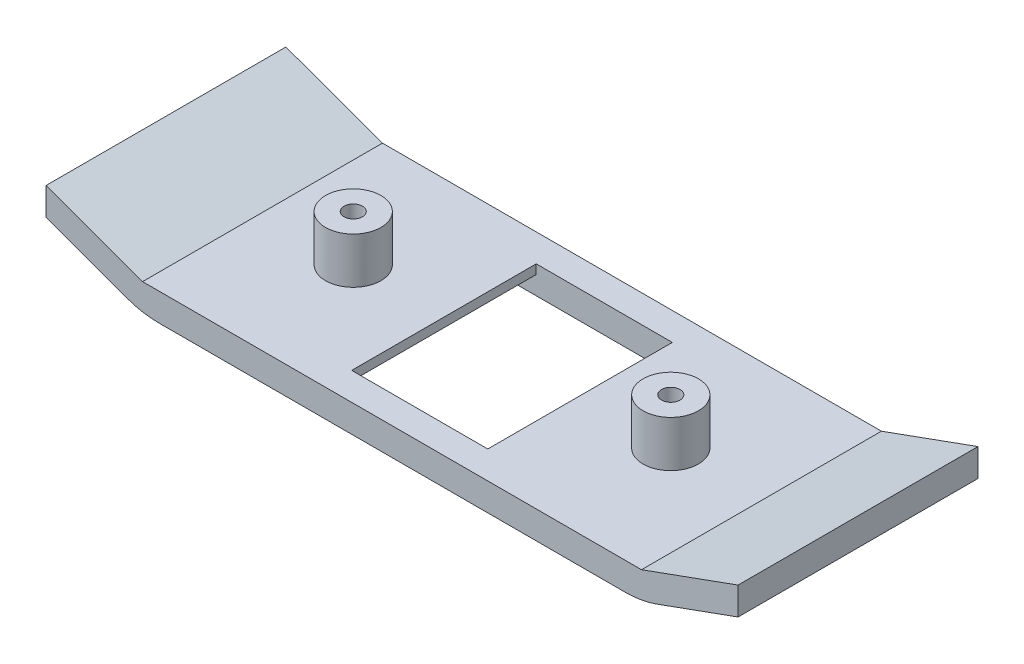
SolidWorks part; units mm, degrees
material "1060 Alloy"
ref_plane "Front Plane" through (0, 0, 0) normal (0, 0, 1) x (1, 0, 0)
ref_plane "Top Plane" through (0, 0, 0) normal (0, 1, 0) x (1, 0, 0)
ref_plane "Right Plane" through (0, 0, 0) normal (1, 0, 0) x (0, 0, -1)
sketch "Sketch1" plane through (0, 0, 0) normal (0, 0, 1) x (1, 0, 0)
  line L0 (0, 0) -> (0, 3) construction
  line L2 (27.0353, 0) -> (-27.0353, 0)
  line L4 (-27.0353, 0) -> (-37.5, 3.7906)
  line L6 (-37.5, 3.7906) -> (-37.5, 6.7906)
  line L7 (-37.5, 6.7906) -> (-27.0353, 3)
  line L9 (-27.0353, 3) -> (27.0353, 3)
  line L12 (-27.0353, 0) -> (-27.0353, 3) construction
  line L15 (27.0353, 0) -> (37.5, 3.7906)
  line L16 (37.5, 3.7906) -> (37.5, 6.7906)
  line L17 (37.5, 6.7906) -> (27.0353, 3)
  dimension "D1" = 3
extrude "Boss-Extrude1" add sketch "Sketch1" along normal offset from surface (26 mm away) 1
sketch "Sketch2" plane through (0, 0, 0) normal (0, -1, 0) x (1, 0, 0)
  line L1 (37.5, 23) -> (-37.5, 23)
  line L2 (37.5, 26) -> (37.5, 0) construction
  line L3 (7.375, 23) -> (37.5, 23) construction
  line L4 (-37.5, 26) -> (-37.5, 0) construction
  line L8 (-37.5, 23) -> (-7.375, 23) construction
  line L9 (-37.5, 23) -> (-37.5, 3)
  line L10 (-7.375, 3) -> (-37.5, 3) construction
  line L11 (-37.5, 3) -> (37.5, 3)
  line L12 (37.5, 3) -> (7.375, 3) construction
  line L13 (37.5, 3) -> (37.5, 23)
extrude "Cut-Extrude1" cut sketch "Sketch2" against normal blind 1
sketch "Sketch4" plane through (0, 1, 0) normal (0, -1, 0) x (1, 0, 0)
  line L0 (-37.5, 23) -> (37.5, 23)
  line L1 (-37.5, 26) -> (-37.5, 0) construction
  line L2 (-37.5, 23) -> (-7.375, 23) construction
  line L3 (7.375, 23) -> (37.5, 23) construction
  line L4 (37.5, 26) -> (37.5, 0) construction
  line L5 (37.5, 23) -> (37.5, 3)
  line L6 (37.5, 3) -> (-37.5, 3)
  line L7 (-7.375, 3) -> (-37.5, 3) construction
  line L8 (-37.5, 3) -> (-37.5, 23)
extrude "Cut-Extrude2" cut sketch "Sketch4" against normal blind 1
sketch "Sketch5" plane through (0, 2, 0) normal (0, -1, 0) x (1, 0, 0)
  line L0 (7.375, 23) -> (7.375, 3) construction
  line L1 (-7.375, 23) -> (7.375, 23) construction
  line L2 (-7.375, 3) -> (-7.375, 23) construction
  line L3 (7.375, 3) -> (-7.375, 3) construction
  line L4 (7.375, 23) -> (7.375, 3)
  line L5 (-7.375, 23) -> (7.375, 23)
  line L6 (-7.375, 3) -> (-7.375, 23)
  line L7 (7.375, 3) -> (-7.375, 3)
extrude "Cut-Extrude3" cut sketch "Sketch5" against normal through all
sketch "Sketch6" plane through (0, 3, 0) normal (0, 1, 0) x (1, 0, 0)
  line L0 (-27.0353, -13) -> (-7.375, -13) construction
  line L1 (-27.0353, -26) -> (-27.0353, 0) construction
  line L3 (0, 0) -> (0, -26) construction
  line L6 (-27.0353, -26) -> (27.0353, -26) construction
  line L7 (-7.375, -23) -> (-7.375, -3) construction
  circle A0 centre (-17.2051, -13) radius 1
  circle A4 centre (-17.2051, -13) radius 3
  circle A5 centre (17.2051, -13) radius 1
  circle A6 centre (17.2051, -13) radius 3
  dimension "D2" = 2
  dimension "D1" = 2
extrude "Boss-Extrude2" add sketch "Sketch6" along normal blind 5
fillet "Fillet1" radius 10 4 edges at (27.0353, 0, 1.5) (27.0353, 0, 24.5) (-27.0353, 0, 1.5) (-27.0353, 0, 24.5)
